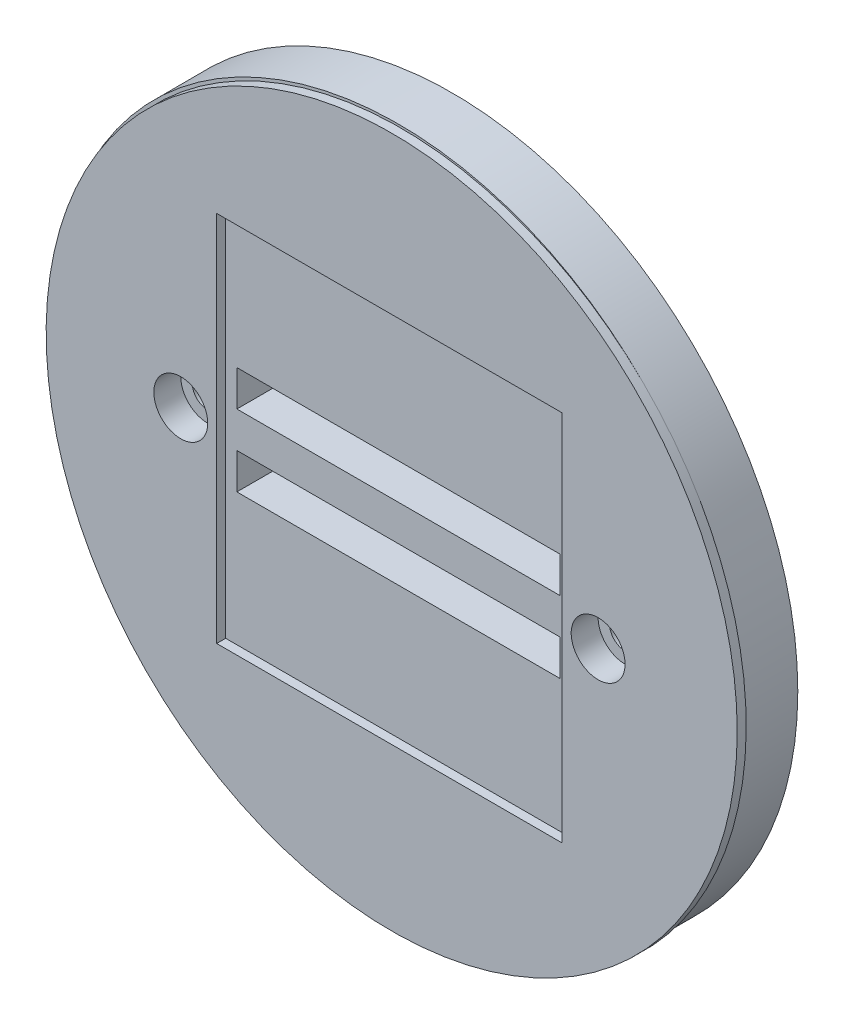
SolidWorks part; units mm, degrees
material "ABS"
ref_plane "Front Plane" through (0, 0, 0) normal (0, 0, 1) x (1, 0, 0)
ref_plane "Top Plane" through (0, 0, 0) normal (0, 1, 0) x (1, 0, 0)
ref_plane "Right Plane" through (0, 0, 0) normal (1, 0, 0) x (0, 0, -1)
sketch "Sketch1" plane through (0, 0, 0) normal (0, 0, 1) x (1, 0, 0)
  line L0 (18, 6) -> (18, 2)
  line L2 (-18, 6) -> (18, 6)
  line L3 (18, -2) -> (-18, -2)
  line L4 (-18, 2) -> (-18, 6)
  line L5 (-18, -2) -> (-18, -6)
  line L6 (-18, -6) -> (18, -6)
  line L7 (18, -6) -> (18, -2)
  line L8 (18, 2) -> (-18, 2)
  circle A0 centre (-23.25, 0) radius 1.725
  circle A1 centre (0, 0) radius 34.7 construction
  circle A2 centre (23.25, 0) radius 1.725
  circle A6 centre (0, 0) radius 38.5
  dimension "D2" = 69.4
  dimension "D3" = 18
  dimension "D6" = 18
  dimension "D7" = 23.25
  dimension "D4" = 23.25
  dimension "D5" = 77
  dimension "D10" = 3.45
  dimension "D8" = 3.45
extrude "Main Flange Coupling" add sketch "Sketch1" against normal blind 6
sketch "Sketch2" plane through (0, 0, 0) normal (0, 0, 1) x (1, 0, 0)
  line L0 (-19.25, 20.75) -> (19.25, 20.75)
  line L1 (-19.25, 20.75) -> (-19.25, -20.75)
  line L2 (-19.25, -20.75) -> (19.25, -20.75)
  line L3 (19.25, 20.75) -> (19.25, -20.75)
  line L4 (-19.25, 20.75) -> (19.25, -20.75) construction
  line L5 (-19.25, -20.75) -> (19.25, 20.75) construction
  circle A0 centre (0.25, -0.25) radius 38.5
  circle A1 centre (-23.25, 0) radius 1.5
  circle A2 centre (23.25, 0) radius 1.5
  dimension "D3" = 77
  dimension "D4" = 3
  dimension "D5" = 3
  dimension "D1" = 38.5
  dimension "D2" = 41.5
  dimension "D6" = 21
  dimension "D7" = 19
extrude "Boss-Extrude1" add sketch "Sketch2" along normal blind 1
sketch "Sketch3" plane through (0, 0, 1) normal (0, 0, 1) x (1, 0, 0)
  circle A0 centre (-23.25, 0) radius 3
  circle A1 centre (23.25, 0) radius 3
  dimension "D1" = 6
  dimension "D2" = 6
extrude "Cut-Extrude1" cut sketch "Sketch3" against normal blind 3
